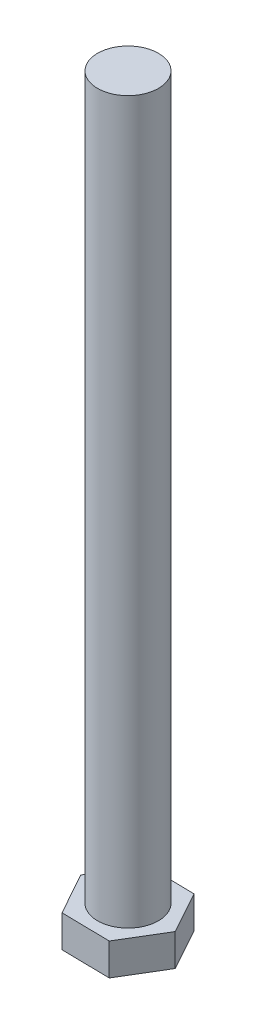
SolidWorks part; units mm, degrees
ref_plane "Front Plane" through (0, 0, 0) normal (0, 0, 1) x (1, 0, 0)
ref_plane "Top Plane" through (0, 0, 0) normal (0, 1, 0) x (1, 0, 0)
ref_plane "Right Plane" through (0, 0, 0) normal (1, 0, 0) x (0, 0, -1)
sketch "Sketch1" plane through (0, 0, 0) normal (0, 1, 0) x (1, 0, 0)
  line L1 (1.452, -2.6258) -> (3, -0.0554)
  line L2 (3, -0.0554) -> (1.548, 2.5704)
  line L3 (1.548, 2.5704) -> (-1.452, 2.6258)
  line L4 (-1.452, 2.6258) -> (-3, 0.0554)
  line L5 (-3, 0.0554) -> (-1.548, -2.5704)
  line L6 (-1.548, -2.5704) -> (1.452, -2.6258)
  circle A0 centre (0, 0) radius 2.5985 construction
  dimension "D1" = 6
extrude "Boss-Extrude1" add sketch "Sketch1" along normal blind 2
sketch "Sketch2" plane through (0, 2, 0) normal (0, 1, 0) x (1, 0, 0)
  circle A0 centre (0, 0) radius 1.9
  dimension "D1" = 3.8
extrude "Boss-Extrude2" add sketch "Sketch2" along normal blind 45
